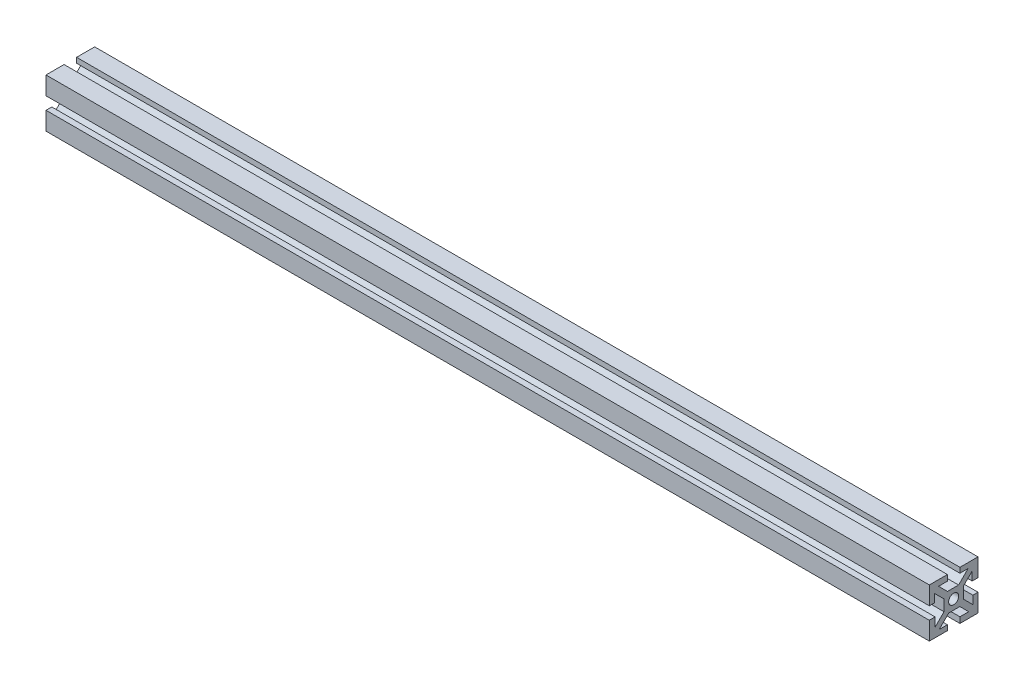
SolidWorks part; units mm, degrees
ref_plane "Front Plane" through (0, 0, 0) normal (0, 0, 1) x (1, 0, 0)
ref_plane "Top Plane" through (0, 0, 0) normal (0, 1, 0) x (1, 0, 0)
ref_plane "Right Plane" through (0, 0, 0) normal (1, 0, 0) x (0, 0, -1)
sketch "Sketch1" plane through (0, 0, 0) normal (1, 0, 0) x (0, 0, -1)
  line L0 (2.5534, 5) -> (7.4749, 9.9215)
  line L1 (-5, 5) -> (5, 5)
  line L2 (-5, 5) -> (-5, -5)
  line L3 (-5, -5) -> (5, -5)
  line L4 (5, 5) -> (5, -5)
  line L5 (-5, 5) -> (5, -5) construction
  line L6 (-5, -5) -> (5, 5) construction
  line L7 (7.4749, 9.9215) -> (9.5962, 7.8001)
  line L8 (9.5962, 7.8001) -> (5, 3.2039)
  line L9 (5, 5) -> (13.6489, 13.6489) construction
  line L10 (7.4749, 9.9215) -> (3.24, 9.9215)
  line L11 (3.24, 9.9215) -> (3.24, 12.5962)
  line L12 (3.24, 12.5962) -> (12.5962, 12.5962)
  line L13 (9.5962, 7.8001) -> (9.5962, 3.24)
  line L14 (9.5962, 3.24) -> (12.5962, 3.24)
  line L15 (12.5962, 3.24) -> (12.5962, 12.5962)
  line L17 (0, 0) -> (0, 24.089) construction
  line L18 (0, 0) -> (23.75, 0) construction
  circle A0 centre (0, 0) radius 2.605
  point P0 (0, 0)
  dimension "D1" = 5.21
  dimension "D2" = 10
  dimension "D3" = 10
  dimension "D4" = 3
  dimension "D5" = 1.27
  dimension "D6" = 6.5
  dimension "D7" = 3.24
  dimension "D8" = 3.24
  dimension "D9" = 3
extrude "Boss-Extrude1" add sketch "Sketch1" along normal blind 457.2 contours L4 L1 L2 L3 A0 | L8 L7 L0 L1 L4 | L14 L15 L12 L11 L10 L7 L13 region at (0, 4.8586, -3.7767) region at (0, 6.7479, -6.3823) region at (0, 9.18, -9.3105)
ref_axis "Axis1" through (0, 0, 0) along (1, 0, 0)
pattern_circular "CirPattern1" count 4 over 360 about axis through (0, 0, 0) along (1, 0, 0) of "Boss-Extrude1"
